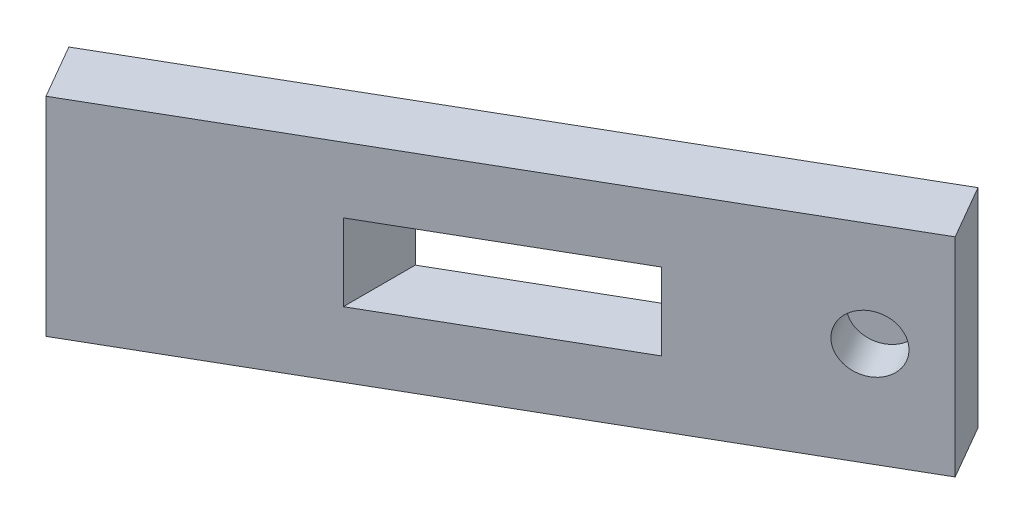
SolidWorks part; units mm, degrees
ref_plane "前基準面" through (0, 0, 0) normal (0, 0, 1) x (1, 0, 0)
ref_plane "上基準面" through (0, 0, 0) normal (0, 1, 0) x (1, 0, 0)
ref_plane "右基準面" through (0, 0, 0) normal (1, 0, 0) x (0, 0, -1)
sketch "草圖1" plane through (0, 0, 0) normal (0, 1, 0) x (1, 0, 0)
  line L0 (-24.4175, -5.9381) -> (-25.9175, -3.34)
  line L1 (-25.9175, -3.34) -> (1.7953, 12.66)
  line L2 (1.7953, 12.66) -> (3.2953, 10.0619)
  line L3 (3.2953, 10.0619) -> (-24.4175, -5.9381)
extrude "填料-伸長1" add sketch "草圖1" along normal blind 5 and the other way blind 5
sketch "草圖2" plane through (0, 0, 0) normal (0, 1, 0) x (1, 0, 0)
  line L0 (-15.3563, -0.7066) -> (-15.3563, 2.4)
  line L1 (-15.3563, -0.7066) -> (-5.6563, 4.8937)
  line L2 (-5.6563, 8.3578) -> (-5.6563, 4.8937)
  line L3 (1.7953, 12.66) -> (-25.9175, -3.34) construction
  line L4 (-24.4175, -5.9381) -> (3.2953, 10.0619) construction
  line L5 (-5.6563, 8.3578) -> (-15.3563, 2.7575)
  line L6 (-15.3563, 2.7575) -> (-15.3563, 2.4)
  dimension "D1" = 9.7
extrude "除料-伸長1" cut sketch "草圖2" against normal mid plane 3.7 contours L0 region at (-10.5063, 0, -3.8256)
sketch "草圖3" plane through (-3.5331, 0, -6.1195) normal (0.5, 0, 0.866) x (0.866, 0, -0.5)
  line L2 (7.8848, -5) -> (7.8848, 5) construction
  circle A0 centre (4.8848, 0) radius 1.375
  dimension "D1" = 2.75
  dimension "D2" = 3
extrude "除料-伸長2" cut sketch "草圖3" against normal blind 2
